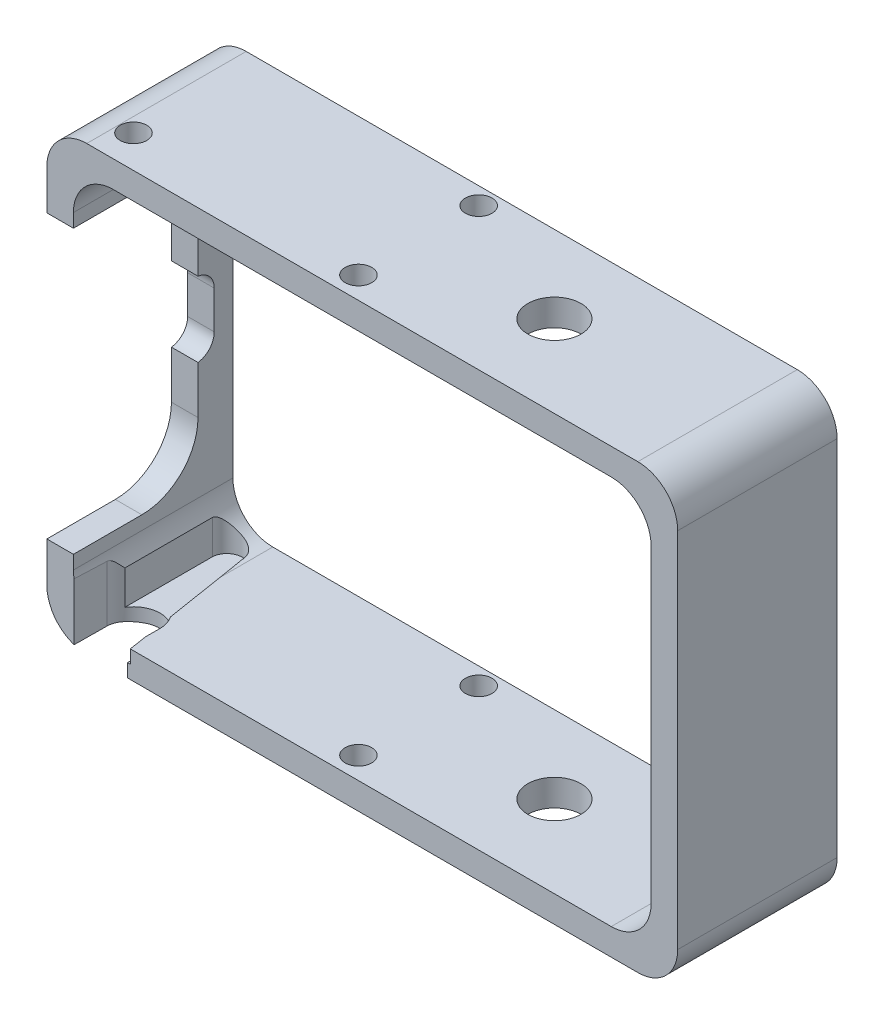
SolidWorks part; units mm, degrees
ref_plane "Alzado" through (0, 0, 0) normal (0, 0, 1) x (1, 0, 0)
ref_plane "Planta" through (0, 0, 0) normal (0, 1, 0) x (1, 0, 0)
ref_plane "Vista lateral" through (0, 0, 0) normal (1, 0, 0) x (0, 0, -1)
sketch "Croquis1" plane through (0, 0, 0) normal (0, 0, 1) x (1, 0, 0)
  line L0 (36.0507, -11.25) -> (-54.9, -11.25) construction
  line L1 (36.0507, -11.25) -> (36.0507, 51.35) construction
  line L2 (-54.9, -11.25) -> (-54.9, 51.35) construction
  line L3 (36.0507, 51.35) -> (-54.9, 51.35) construction
  line L4 (38.0507, -13.25) -> (-56.9, -13.25)
  line L5 (-56.9, -13.25) -> (-56.9, 53.35)
  line L6 (38.0507, 53.35) -> (-56.9, 53.35)
  line L7 (38.0507, -13.25) -> (38.0507, 53.35)
  line L8 (34.0507, -9.25) -> (-52.9, -9.25)
  line L9 (-52.9, -9.25) -> (-52.9, 49.35)
  line L10 (34.0507, 49.35) -> (-52.9, 49.35)
  line L11 (34.0507, -9.25) -> (34.0507, 49.35)
  line L12 (15.5, -9.25) -> (-18.5, -9.25) construction
  line L15 (18.5, 49.35) -> (15.5, 49.35) construction
  line L16 (-47.9, 41.85) -> (-47.9, 39.85) construction
  dimension "D3" = 0
  dimension "D4" = 5
  dimension "D5" = 0
  dimension "D1" = 2
  dimension "D2" = 2
extrude "Saliente-Extruir1" add sketch "Croquis1" against normal blind 23 and the other way blind 1
sketch "Croquis2" plane through (0, -13.25, 0) normal (0, -1, 0) x (-1, 0, 0)
  line L0 (48.7666, -1) -> (48.7666, 23) construction
  line L1 (56.9, -1) -> (-38.0507, -1) construction
  line L2 (56.9, 23) -> (-38.0507, 23) construction
  line L3 (44.7666, 3.9048) -> (44.7666, -1.027)
  line L4 (52.7666, 3.9048) -> (52.7997, -1)
  line L5 (44.7666, -1.027) -> (52.7997, -1)
  arc A0 (52.7666, 3.9048) -> (44.7666, 3.9048) centre (48.7666, 3.9048) ccw
  arc A1 (54.6306, 1.4684) -> (54.6722, 6.2385) centre (48.7666, 3.9048) ccw construction
  arc A2 (50.0924, 10.1148) -> (45.3947, 9.2855) centre (48.7666, 3.9048) ccw construction
extrude "Cortar-Extruir1" cut sketch "Croquis2" against normal up to next
sketch "Croquis4" plane through (-52.9, 0, 0) normal (1, 0, 0) x (0, 0, -1)
  line L0 (-1, 20.05) -> (23, 20.05) construction
  line L1 (-1, -13.25) -> (-1, 53.35) construction
  line L2 (23, -13.25) -> (23, 53.35) construction
sketch "Croquis5" plane through (-56.9, 0, 0) normal (-1, 0, 0) x (0, 0, 1)
  line L0 (-9.3, 32.85) -> (-9.3, 7.25) construction
  line L2 (-17.75, 32.85) -> (-17.75, 7.25)
  line L3 (-9.3, 41.3) -> (1, 41.3)
  line L4 (1, 53.35) -> (1, -13.25) construction
  line L5 (1, 41.3) -> (1, -1.2)
  line L6 (1, -1.2) -> (-9.3, -1.2)
  arc A0 (-9.3, 41.3) -> (-17.75, 32.85) centre (-9.3, 32.85) ccw
  arc A1 (-17.75, 7.25) -> (-9.3, -1.2) centre (-9.3, 7.25) ccw
  point P4 (-9.3, 20.05)
  point P5 (0, 0)
  dimension "D2" = 42.5
  dimension "D3" = 18.75
extrude "Cortar-Extruir2" cut sketch "Croquis5" against normal up to next
sketch "Croquis6" plane through (-56.9, 0, 0) normal (-1, 0, 0) x (0, 0, 1)
  line L0 (-17.4, 22.9) -> (-17.4, 17.2) construction
  line L1 (-14.6069, 22.9) -> (-14.6069, 17.2)
  line L2 (-20.1931, 22.9) -> (-20.1931, 17.2)
  arc A0 (-14.6069, 22.9) -> (-20.1931, 22.9) centre (-17.4, 22.9) ccw
  arc A1 (-20.1931, 17.2) -> (-14.6069, 17.2) centre (-17.4, 17.2) ccw
  point P4 (-17.4, 20.05)
extrude "Cortar-Extruir3" cut sketch "Croquis6" against normal up to next
sketch "Croquis9" plane through (0, -9.25, 0) normal (0, 1, 0) x (1, 0, 0)
  line L0 (-52.1673, 19.2012) -> (-52.1673, -1)
  line L1 (-47.5442, 19.0656) -> (-44.3386, -1)
  line L3 (-52.9, -1) -> (-52.7997, -1) construction
  line L4 (-44.3386, -1) -> (-52.1673, -1)
  arc A1 (-47.5442, 19.0656) -> (-52.1673, 19.2012) centre (-49.8577, 19.0656) ccw
  circle A3 centre (-48.7666, 3.9048) radius 4 construction
  point P2 (-44.3386, -1)
  dimension "D1" = 3.5988
extrude "Cortar-Extruir5" cut sketch "Croquis9" against normal blind 2
sketch "Croquis10" plane through (0, 53.35, 0) normal (0, 1, 0) x (1, 0, 0)
  circle A0 centre (-48.7666, 3.9048) radius 2
  dimension "D1" = 4
extrude "Cortar-Extruir6" cut sketch "Croquis10" against normal up to next
fillet "Redondeo1" radius 6 2 edges at (-56.9, -13.25, -11) (-56.9, 53.35, -11)
fillet "Redondeo2" radius 6 2 edges at (-52.9, -9.25, -11) (-52.9, 49.35, -11)
fillet "Redondeo3" radius 6 4 edges at (34.0507, 49.35, -11) (38.0507, -13.25, -11) (38.0507, 53.35, -11) (34.0507, -9.25, -11)
sketch "Croquis12" plane through (0, -13.25, 0) normal (0, -1, 0) x (1, 0, 0)
  circle A0 centre (7.15, -11.35) radius 4
  circle A1 centre (-13.3, -2.3) radius 2
  circle A2 centre (-13.3, -20.4) radius 2
extrude "Cortar-Extruir7" cut sketch "Croquis12" against normal blind 70
